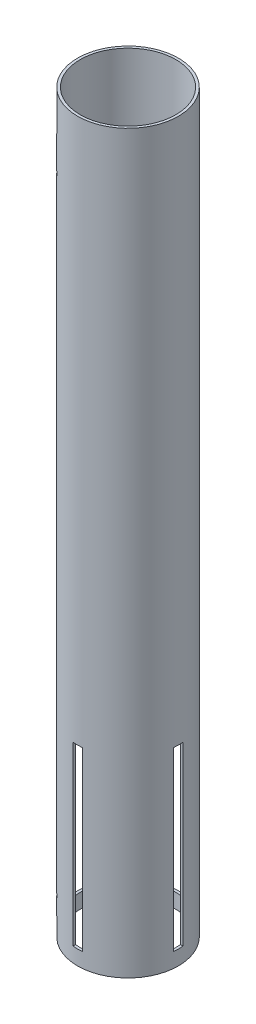
SolidWorks part; units mm, degrees
material "S-Glass Fiber"
ref_plane "Front Plane" through (0, 0, 0) normal (0, 0, 1) x (1, 0, 0)
ref_plane "Top Plane" through (0, 0, 0) normal (0, 1, 0) x (1, 0, 0)
ref_plane "Right Plane" through (0, 0, 0) normal (1, 0, 0) x (0, 0, -1)
ref_axis "ROCKET AXIS" through (0, -25, 0) along (0, 1, 0)
sketch "Sketch1" plane through (0, 0, 0) normal (0, 1, 0) x (1, 0, 0)
  circle A0 centre (0, 0) radius 32.5
  circle A1 centre (0, 0) radius 34.25
  dimension "D1" = 65
  dimension "D2" = 68.5
extrude "BULK" add sketch "Sketch1" along normal blind 500
ref_plane "LAUNCH LUG PLANE" through (0, 0, 0) normal (-0.7071, 0, 0.7071) x (0.7071, 0, 0.7071)
sketch "Sketch2" plane through (0, 0, 0) normal (-0.7071, 0, 0.7071) x (0.7071, 0, 0.7071)
  circle A0 centre (0, 25) radius 1.75
  circle A1 centre (0, 450) radius 1.75
  dimension "D1" = 3.5
  dimension "D2" = 25
  dimension "D3" = 450
extrude "LAUNCH LUG SCREW HOLES" cut sketch "Sketch2" along normal through all
sketch "Sketch3" plane through (0, 0, 0) normal (0, 0, 1) x (1, 0, 0)
  line L1 (-3.25, 130) -> (3.25, 130)
  line L2 (-3.25, 130) -> (-3.25, 10)
  line L3 (-3.25, 10) -> (3.25, 10)
  line L4 (3.25, 130) -> (3.25, 10)
  point P4 (0, 10)
  dimension "D1" = 10
  dimension "D2" = 6.5
  dimension "D3" = 120
extrude "THRU WALL FIN CUTS" cut sketch "Sketch3" against normal through all both and the other way through all
pattern_circular "THRU WALL FIN CUT PATTERN" count 2 every 90 about axis through (0, -25, 0) along (0, 1, 0) of "THRU WALL FIN CUTS"
